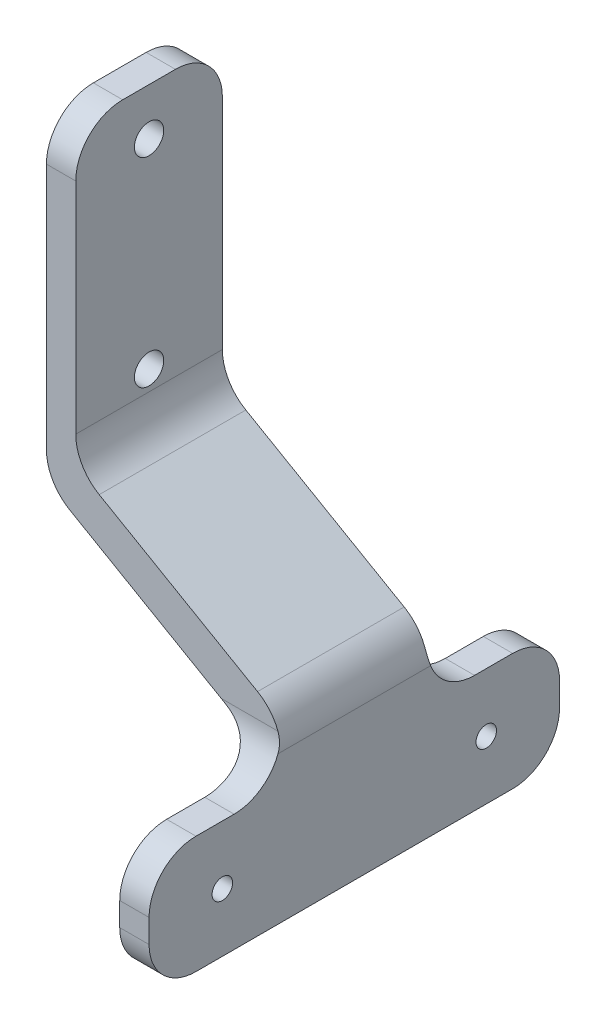
SolidWorks part; units mm, degrees
ref_plane "Front Plane" through (0, 0, 0) normal (0, 0, 1) x (1, 0, 0)
ref_plane "Top Plane" through (0, 0, 0) normal (0, 1, 0) x (1, 0, 0)
ref_plane "Right Plane" through (0, 0, 0) normal (1, 0, 0) x (0, 0, -1)
sketch "Sketch1" plane through (0, 0, 0) normal (0, 0, 1) x (1, 0, 0)
  line L0 (0, 0) -> (0, 25)
  line L1 (0, 25) -> (30, 25)
  line L2 (30, 25) -> (30, 0)
  line L3 (30, 0) -> (0, 0)
  dimension "D1" = 30
  dimension "D2" = 25
extrude "Boss-Extrude1" add sketch "Sketch1" along normal mid plane 25
sketch "Sketch2" plane through (30, 0, 0) normal (1, 0, 0) x (0, 0, -1)
  line L1 (-35, -25) -> (35, -25)
  line L2 (-35, -25) -> (-35, -5)
  line L3 (-35, -5) -> (35, -5)
  line L4 (35, -25) -> (35, -5)
  line L5 (-35, -25) -> (35, -5) construction
  line L6 (-35, -5) -> (35, -25) construction
  line L7 (12.5, 0) -> (12.5, 25) construction
  line L8 (-12.5, 25) -> (12.5, 25) construction
  line L9 (-12.5, 0) -> (12.5, 0) construction
  line L11 (-12.5, 25) -> (12.5, 25)
  line L12 (-12.5, 25) -> (-12.5, -5)
  line L13 (-12.5, -5) -> (12.5, -5)
  line L14 (12.5, 25) -> (12.5, -5)
  point P0 (0, -15)
  point P10 (0, 25)
  line M5 (12.5, 0) -> (12.5, 25)
  line M6 (12.5, 25) -> (-12.5, 25)
  line M7 (-12.5, 25) -> (-12.5, 0)
  line M8 (-12.5, 0) -> (12.5, 0)
  dimension "D1" = 70
  dimension "D2" = 20
  dimension "D3" = 5
extrude "Boss-Extrude2" add sketch "Sketch2" along normal blind 5 contours M8 M5 M6 M7 | L14 L12 L3 M8 | L1 L4 L3 L2 region at (30, -15, 0) region at (30, -2.5, 0) region at (30, 12.5, 0)
sketch "Sketch5" plane through (0, 0, 0) normal (-1, 0, 0) x (0, 0, 1)
  line L0 (12.5, 25) -> (12.5, 0) construction
  line L1 (-12.5, 0) -> (12.5, 0)
  line L2 (-12.5, 0) -> (-12.5, 75)
  line L3 (-12.5, 75) -> (12.5, 75)
  line L4 (12.5, 0) -> (12.5, 75)
  dimension "D1" = 75
extrude "Boss-Extrude4" add sketch "Sketch5" along normal blind 5 contours L2 L1 L4 L3
sketch "Sketch6" plane through (35, 0, 0) normal (1, 0, 0) x (0, 0, -1)
  line L0 (-22.5, -15) -> (22.5, -15) construction
  line L1 (-35, -25) -> (-35, -5) construction
  circle A0 centre (-22.5, -15) radius 1.75
  circle A1 centre (22.5, -15) radius 1.75
  point P4 (0, -15)
  point P8 (-35, -15)
  dimension "D1" = 3.5
  dimension "D2" = 45
extrude "Cut-Extrude1" cut sketch "Sketch6" against normal through all
sketch "Sketch7" plane through (0, 0, 0) normal (1, 0, 0) x (0, 0, -1)
  line L0 (12.5, 75) -> (-12.5, 75) construction
  line L1 (12.5, 25) -> (-12.5, 25) construction
  circle A0 centre (0, 67) radius 2.5
  circle A1 centre (0, 33) radius 2.5
  point P7 (0, 75)
  dimension "D1" = 5
  dimension "D2" = 8
  dimension "D3" = 8
extrude "Cut-Extrude2" cut sketch "Sketch7" against normal through all
chamfer "Chamfer1" distance 35 angle 30 2 edges at (-5, 0, 0) (35, 25, 0) first distance on face at (12.5, 0, 0) first distance on face at (17.5, 25, 0)
fillet "Fillet1" radius 8 10 edges at (32.5, -25, 35) (32.5, -5, 35) (32.5, -25, -35) (32.5, -5, -35) (30, 0, 0) (35, 4.7927, 0) (-5, 20.2073, 0) (0, 25, 0) (-2.5, 75, 12.5) (-2.5, 75, -12.5)
fillet "Fillet2" radius 8 2 edges at (32.5, -5, -12.5) (32.5, -5, 12.5)
